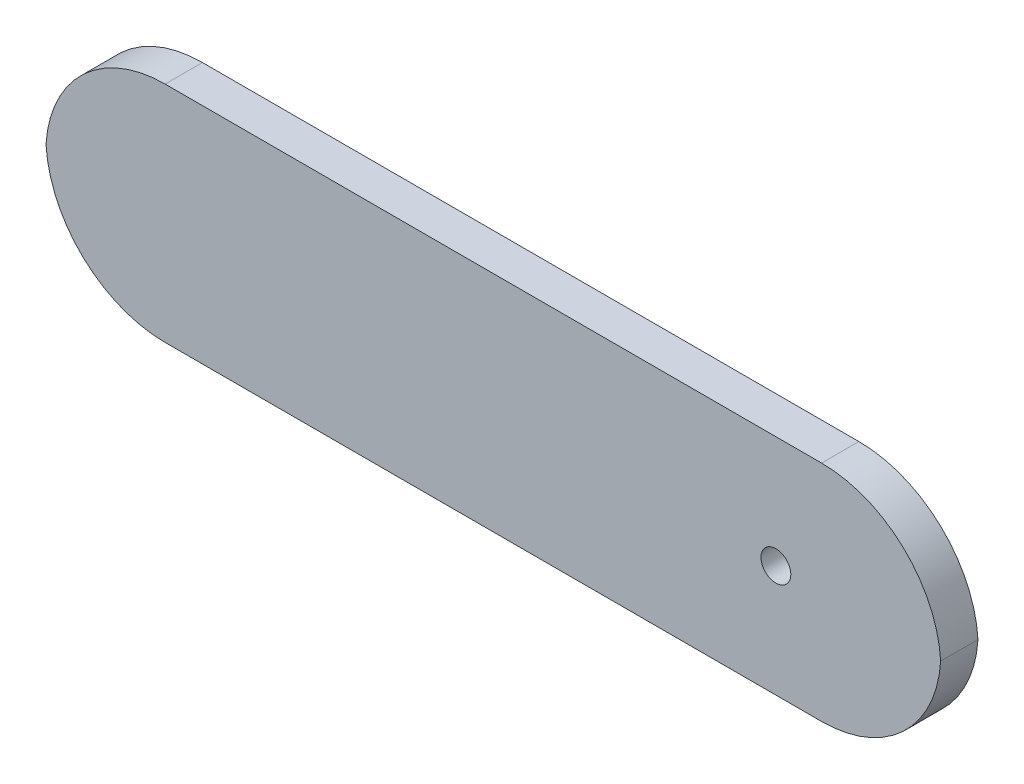
SolidWorks part; units mm, degrees
ref_plane "Front Plane" through (0, 0, 0) normal (0, 0, 1) x (1, 0, 0)
ref_plane "Top Plane" through (0, 0, 0) normal (0, 1, 0) x (1, 0, 0)
ref_plane "Right Plane" through (0, 0, 0) normal (1, 0, 0) x (0, 0, -1)
sketch "Sketch1" plane through (0, 0, 0) normal (0, 0, 1) x (1, 0, 0)
  line L4 (38.1, -9.525) -> (-38.1, -9.525)
  line L5 (38.1, -9.525) -> (38.1, 9.525)
  line L6 (38.1, 9.525) -> (-38.1, 9.525)
  line L7 (-38.1, -9.525) -> (-38.1, 9.525)
  line L8 (38.1, -9.525) -> (-38.1, 9.525) construction
  line L9 (38.1, 9.525) -> (-38.1, -9.525) construction
  point P3 (0, 0)
  dimension "D1" = 76.2
  dimension "D2" = 19.05
extrude "Boss-Extrude1" add sketch "Sketch1" along normal blind 3.175
sketch "Sketch2" plane through (0, 0, 3.175) normal (0, 0, 1) x (1, 0, 0)
  circle A0 centre (24.0513, 0) radius 1.27
  dimension "D1" = 2.54
extrude "Cut-Extrude1" cut sketch "Sketch2" against normal through all
fillet "Fillet1" radius 10.16 4 edges at (-38.1, -9.525, 1.5875) (-38.1, 9.525, 1.5875) (38.1, -9.525, 1.5875) (38.1, 9.525, 1.5875)
